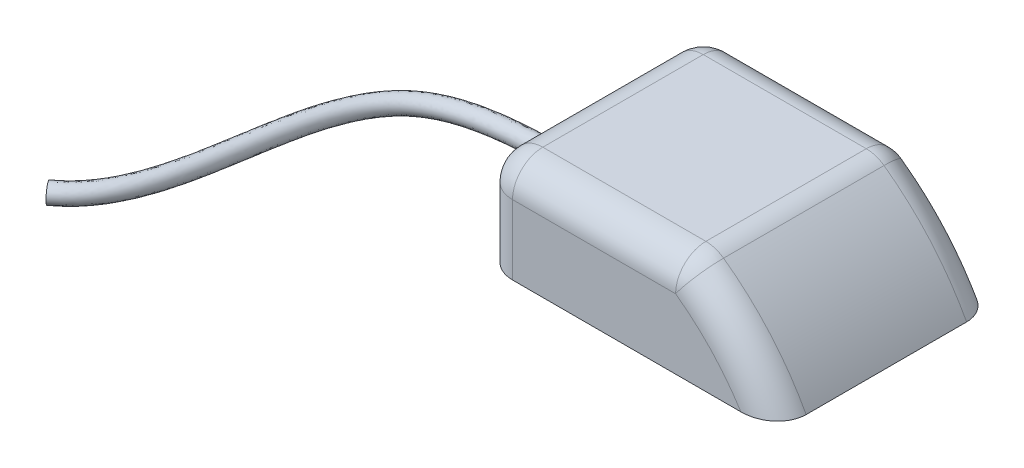
SolidWorks part; units mm, degrees
ref_plane "Спереди" through (0, 0, 0) normal (0, 0, 1) x (1, 0, 0)
ref_plane "Сверху" through (0, 0, 0) normal (0, 1, 0) x (1, 0, 0)
ref_plane "Справа" through (0, 0, 0) normal (1, 0, 0) x (0, 0, -1)
sketch "Sketch1" plane through (0, 0, 0) normal (0, 0, 1) x (1, 0, 0)
  line L0 (0, 0) -> (48.5, 0)
  line L1 (0, 0) -> (0, 16.5)
  line L2 (0, 16.5) -> (33.5, 16.5)
  arc A0 (48.5, 0) -> (33.5, 16.5) centre (7.8895, -21.8504) ccw
  point P6 (27.3834, 16.5)
  point P7 (27.746, 16.5)
  point P8 (33.5, 16.5)
  dimension "D1" = 16.5
  dimension "D2" = 48.5
  dimension "D3" = 15
extrude "Boss-Extrude1" add sketch "Sketch1" against normal blind 36.5
fillet "Fillet1" radius 5 6 edges at (33.5, 16.5, -18.25) (0, 16.5, -18.25) (42.0123, 9.1703, -36.5) (16.75, 16.5, -36.5) (42.0123, 9.1703, 0) (16.75, 16.5, 0)
fillet "Fillet2" radius 5 4 edges at (1.4645, 15.0355, -1.4645) (1.4645, 15.0355, -35.0355) (0, 5.75, 0) (0, 5.75, -36.5)
sketch "Sketch2" plane through (0, 0, 0) normal (-1, 0, 0) x (0, 0, 1)
  line L0 (-31.5, 0) -> (-5, 0) construction
  circle A0 centre (-18.25, 3) radius 1.5
  dimension "D1" = 3
  dimension "D2" = 3
  dimension "D3" = 18.25
ref_plane "Plane1" through (0, 3, 0) normal (0, -1, 0) x (-1, 0, 0)
sketch "Sketch3" plane through (0, 3, 0) normal (0, -1, 0) x (-1, 0, 0)
  line L0 (0, 16.75) -> (0, 19.75) construction
  spline S0 degree 3 poles (0, 18.25) (7.6797, 18.3325) (39.7925, 19.7831) (30.1364, -19.8442) (42.8654, -28.854) knots 0 0 0 0 0.355769 1 1 1 1
  point P2 (32.9194, -11.8353)
sweep "Sweep1" add profiles "Sketch2" path "Sketch3"
